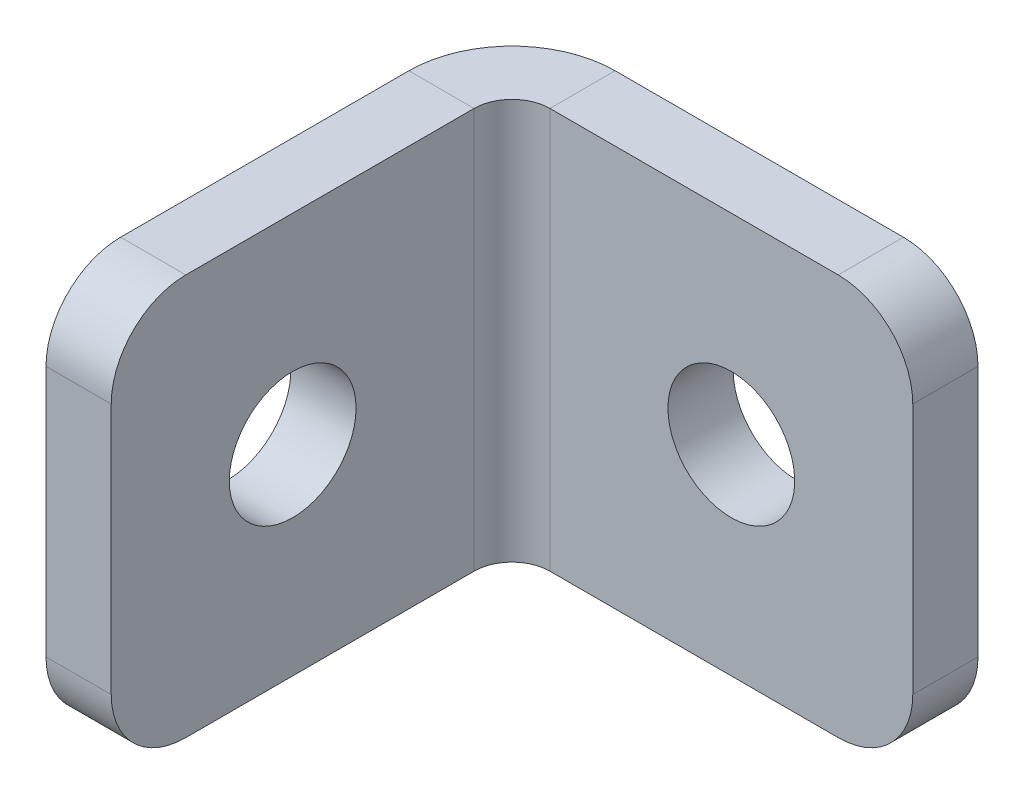
SolidWorks part; units mm, degrees
note: The reader was unsure of these and kept them because the rebuilt part matched: thickness of "Base-Flange1", "Edge-Flange1", "Sheet-Metal2", "Sheet-Metal3", "Sheet-Metal4"; flange length of "Edge-Flange1".
ref_plane "Front Plane" through (0, 0, 0) normal (0, 0, 1) x (1, 0, 0)
ref_plane "Top Plane" through (0, 0, 0) normal (0, 1, 0) x (1, 0, 0)
ref_plane "Right Plane" through (0, 0, 0) normal (1, 0, 0) x (0, 0, -1)
sketch "Sketch1" plane through (0, 0, 0) normal (0, 0, 1) x (1, 0, 0)
  line L1 (0, 0) -> (10.75, 0)
  line L2 (0, 0) -> (0, 10.75)
  line L3 (0, 10.75) -> (10.75, 10.75)
  line L4 (10.75, 0) -> (10.75, 10.75)
  dimension "D1" = 10.75
  dimension "D2" = 10.75
base flange "Base-Flange1" sketch "Sketch1" thickness 1.75 reverse thickness direction no parameters "D1"=1.016
edge flange "Edge-Flange1" sketch "Sketch8" flange angle 90 flange length 10.75 flange position material outside bend radius 1.016 thickness 1.75 relief rectangular parameters "D6"=10
sketch "Sketch8" plane through (0, 0, 0) normal (-1, 0, 0) x (0, -1, 0)
  line L2 (-10.75, 0) -> (-10.75, 10.75)
  line L3 (-10.75, 10.75) -> (0, 10.75)
  line L4 (0, 10.75) -> (0, 0)
  line L7 (-10.75, 0) -> (0, 0) construction
  line L8 (-10.75, 0) -> (0, 0)
bend "EdgeBend1" bend radius 1.016 bend angle 90 parameters "D5"=1
sketch "Sketch9" plane through (0, 0, -1.75) normal (0, 0, 1) x (1, 0, 0)
  line L0 (10.75, 0) -> (10.75, 10.75) construction
  line L1 (1.016, 0) -> (1.016, 10.75) construction
  line L2 (10.75, 0) -> (10.75, 10.75) construction
  line L5 (1.016, 5.375) -> (10.75, 5.375) construction
  line L6 (5.883, 5.375) -> (5.883, 0) construction
  line L7 (1.016, 0) -> (10.75, 0) construction
sketch "Sketch10" plane through (-1.75, 0, 0) normal (1, 0, 0) x (0, 0, -1)
  line L0 (-10.75, 0) -> (-10.75, 10.75) construction
  line L5 (-10.75, 5.375) -> (-1.016, 5.375) construction
  line L6 (-5.883, 5.375) -> (-5.883, 0) construction
  line L9 (-10.75, 0) -> (-10.75, 10.75) construction
  line L10 (-1.016, 10.75) -> (-1.016, 0) construction
  line L11 (-1.016, 0) -> (-10.75, 0) construction
hole_wizard "M3 Clearance Hole1" positions "3DSketch1" profile "Sketch11" hole size "M3" standard "ANSI Metric" end condition up to next
sketch3d "3DSketch1"
  point P0 (5.883, 5.375, -1.75)
  point P3 (-1.75, 5.375, 5.883)
sketch "Sketch11" plane through (5.883, 5.375, -1.75) normal (1, 0, 0) x (0, 1, 0)
  line L0 (0, 0) -> (0, 1.75)
  line L1 (0, 1.75) -> (1.7, 1.75)
  line L2 (1.7, 1.75) -> (1.7, 0)
  line L5 (1.7, 0) -> (0, 0)
  line L11 (0, -6.35) -> (0, 107.95) construction
  dimension "Thru Hole Dia." = 3.4
  dimension "Thru Hole Depth" = 1.75
fillet "Fillet1" radius 2 4 edges at (-0.875, 0, 10.75) (-0.875, 10.75, 10.75) (10.75, 0, -0.875) (10.75, 10.75, -0.875)
sketch "Bend-Lines1" [suppressed] plane through (0, 0, 0) normal (0, 1, 0) x (1, 0, 0)
sketch "Bounding-Box1" [suppressed] plane through (0, 0, 0) normal (0, 1, 0) x (1, 0, 0)
sheet metal parameters "Sheet-Metal2" thickness 1.75 parameters "D1"=1.016, "D7"=1.016
flat pattern "Flat-Pattern2" [suppressed]
sketch "Bend-Lines2" plane through (0, 0, 0) normal (0, 1, 0) x (1, 0, 0)
sketch3d "Bounding-Box2" [suppressed]
  line L0 (-8.75, 50, 0) -> (-8.75, 0, 0) construction
  line L1 (0, 50, 0) -> (0, 0, 0) construction
  line L2 (-8.75, 50, 0) -> (0, 50, 0) construction
  line L3 (-8.75, 0, 0) -> (0, 0, 0) construction
sheet metal parameters "Sheet-Metal3" thickness 1.75 parameters "D1"=1.016, "D7"=1.016
flat pattern "Flat-Pattern2"
sketch "Bend-Lines2" plane through (0, 0, 0) normal (0, 0, 1) x (1, 0, 0)
  line L0 (-0.1809, 40) -> (-0.1809, 0) construction
  line L1 (-0.1809, 40) -> (-0.1809, 0) construction
sketch3d "Bounding-Box2" [suppressed]
  line L0 (8.75, 40, 0) -> (8.75, 0, 0) construction
  line L1 (-9.1119, 40, 0) -> (-9.1119, 0, 0) construction
  line L2 (8.75, 40, 0) -> (-9.1119, 40, 0) construction
  line L3 (8.75, 0, 0) -> (-9.1119, 0, 0) construction
bend of the flat pattern "Flatten-<EdgeBend1>1"
sheet metal parameters "Sheet-Metal4" thickness 1.75 parameters "D1"=1.016, "D7"=1.016
flat pattern "Flat-Pattern2" [suppressed]
sketch "Bend-Lines2" plane through (0, 0, 0) normal (0, 0, 1) x (1, 0, 0)
  line L0 (-0.4692, 10.75) -> (-0.4692, 0) construction
  line L1 (-0.4692, 10.75) -> (-0.4692, 0) construction
sketch3d "Bounding-Box2" [suppressed]
  line L0 (-11.6884, 10.75, 0) -> (10.75, 10.75, 0) construction
  line L1 (-11.6884, 0, 0) -> (10.75, 0, 0) construction
  line L2 (-11.6884, 10.75, 0) -> (-11.6884, 0, 0) construction
  line L3 (10.75, 10.75, 0) -> (10.75, 0, 0) construction
bend of the flat pattern "Flatten-<EdgeBend1>1"
sketch "Sketch10-1" plane through (-0.9384, 0, -1.75) normal (0, 0, 1) x (1, 0, 0)
  line L5 (-10.75, 5.375) -> (-1.016, 5.375) construction
  line L6 (-5.883, 5.375) -> (-5.883, 0) construction
